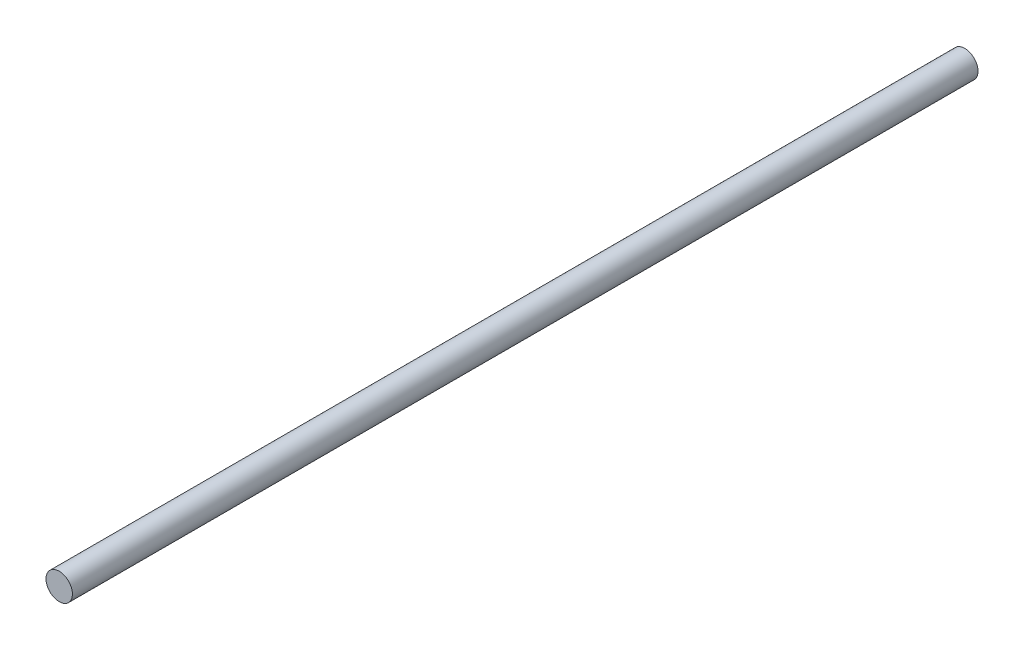
SolidWorks part; units mm, degrees
ref_plane "Plan de face" through (0, 0, 0) normal (0, 0, 1) x (1, 0, 0)
ref_plane "Plan de dessus" through (0, 0, 0) normal (0, 1, 0) x (1, 0, 0)
ref_plane "Plan de droite" through (0, 0, 0) normal (1, 0, 0) x (0, 0, -1)
sketch "Esquisse1" plane through (0, 0, 0) normal (0, 0, 1) x (1, 0, 0)
  circle A0 centre (0, 0) radius 2.45
  dimension "D1" = 4.9
extrude "Boss.-Extru.1" add sketch "Esquisse1" along normal blind 168 contours A0
